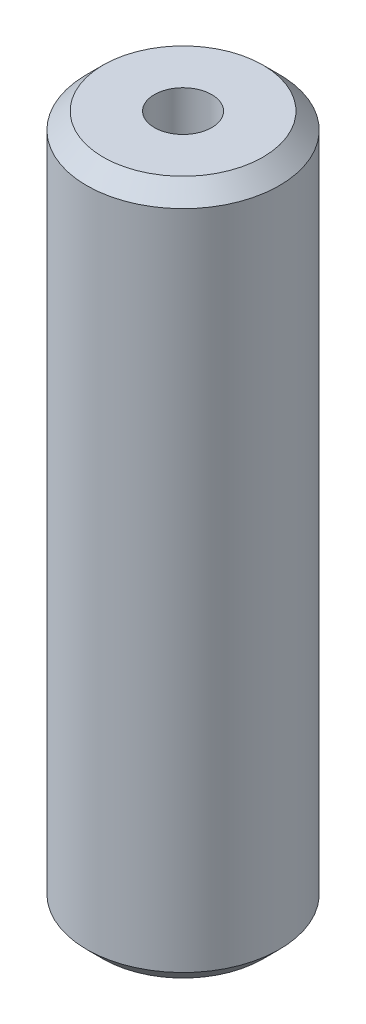
SolidWorks part; units mm, degrees
ref_plane "Front Plane" through (0, 0, 0) normal (0, 0, 1) x (1, 0, 0)
ref_plane "Top Plane" through (0, 0, 0) normal (0, 1, 0) x (1, 0, 0)
ref_plane "Right Plane" through (0, 0, 0) normal (1, 0, 0) x (0, 0, -1)
sketch "Sketch1" plane through (0, 0, 0) normal (0, 1, 0) x (1, 0, 0)
  circle A0 centre (0, 0) radius 17.5
  dimension "SHAFT_OD" = 35
extrude "Boss-Extrude1" add sketch "Sketch1" along normal blind 126.1949
sketch "Sketch2" plane through (0, 0, 0) normal (0, 1, 0) x (1, 0, 0)
  circle A0 centre (0, 0) radius 5.209
  dimension "BORE_D" = 10.418
extrude "Cut-Extrude1" cut sketch "Sketch2" along normal through all
chamfer "Chamfer1" distance 2.9861 angle 45 2 edges at (0, 126.1949, 17.5) (0, 0, 17.5)
